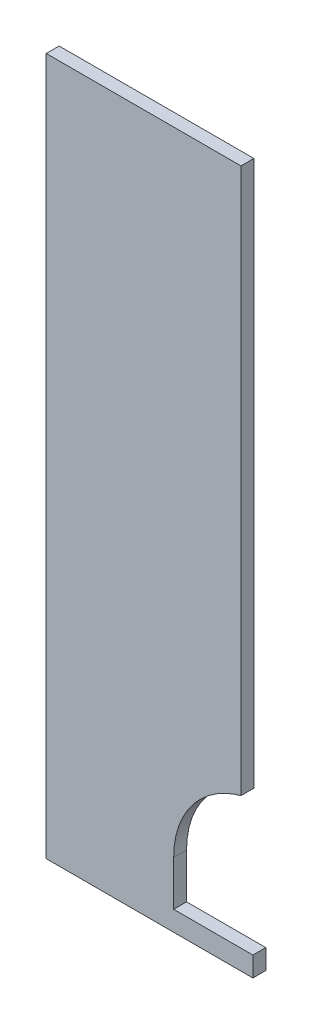
SolidWorks part; units mm, degrees
material "Balsa"
ref_plane "Plan de face" through (0, 0, 0) normal (0, 0, 1) x (1, 0, 0)
ref_plane "Plan de dessus" through (0, 0, 0) normal (0, 1, 0) x (1, 0, 0)
ref_plane "Plan de droite" through (0, 0, 0) normal (1, 0, 0) x (0, 0, -1)
sketch "Esquisse1" plane through (0, 0, 0) normal (0, 0, 1) x (1, 0, 0)
  line L0 (49.3309, 25.1093) -> (120.4109, 25.1093) construction
  line L1 (0, 0) -> (80, 0)
  line L2 (0, 0) -> (0, 270)
  line L3 (0, 270) -> (75.3983, 270)
  line L4 (75.3983, 58.8433) -> (75.3983, 270)
  line L5 (49.3309, 25.1093) -> (49.3309, 7.7039)
  line L6 (49.3309, 7.7039) -> (80, 7.7039)
  line L7 (80, 7.7039) -> (80, 0)
  ellipse E0 centre (84.8709, 25.1093) end of major axis (120.4109, 25.1093) minor radius 35 (49.3309, 25.1093) -> (75.3983, 58.8433) cw
  point P5 (84.8709, 25.1093)
  dimension "D1" = 80
  dimension "D2" = 270
  dimension "D4" = 70
  dimension "D5" = 71.08
extrude "Boss.-Extru.1" add sketch "Esquisse1" along normal blind 5
